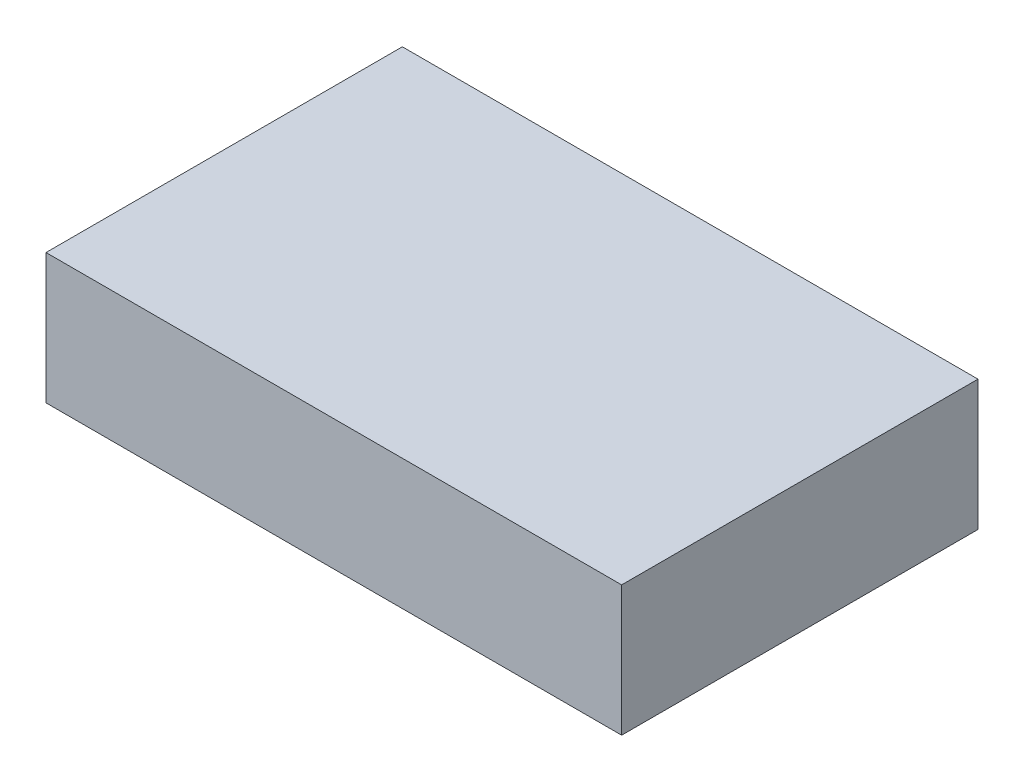
SolidWorks part; units mm, degrees
ref_plane "前视基准面" through (0, 0, 0) normal (0, 0, 1) x (1, 0, 0)
ref_plane "上视基准面" through (0, 0, 0) normal (0, 1, 0) x (1, 0, 0)
ref_plane "右视基准面" through (0, 0, 0) normal (1, 0, 0) x (0, 0, -1)
sketch "草图1" plane through (0, 0, 0) normal (0, 1, 0) x (1, 0, 0)
  line L1 (-21, 13) -> (21, 13)
  line L2 (-21, 13) -> (-21, -13)
  line L3 (-21, -13) -> (21, -13)
  line L4 (21, 13) -> (21, -13)
  line L5 (-21, 13) -> (21, -13) construction
  line L6 (-21, -13) -> (21, 13) construction
  point P0 (0, 0)
  dimension "D1" = 42
  dimension "D2" = 26
extrude "凸台-拉伸1" add sketch "草图1" along normal blind 9.5
